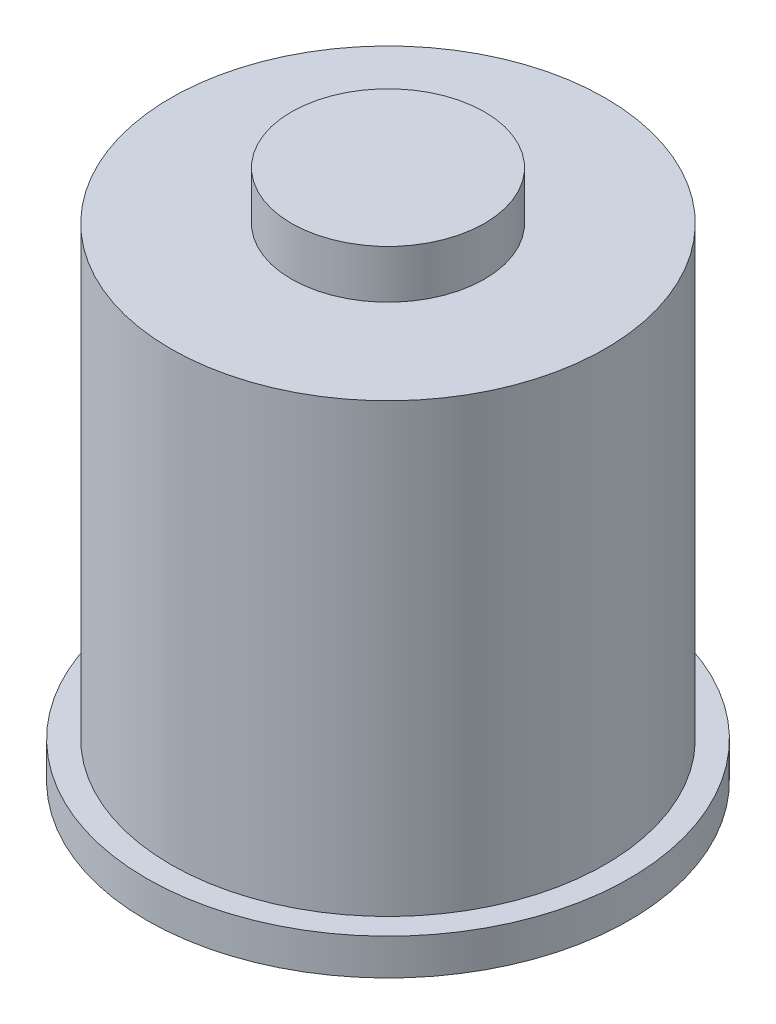
SolidWorks part; units mm, degrees
ref_plane "Plan de face" through (0, 0, 0) normal (0, 0, 1) x (1, 0, 0)
ref_plane "Plan de dessus" through (0, 0, 0) normal (0, 1, 0) x (1, 0, 0)
ref_plane "Plan de droite" through (0, 0, 0) normal (1, 0, 0) x (0, 0, -1)
sketch "Esquisse1" plane through (0, 0, 0) normal (1, 0, 0) x (0, 0, -1)
  line L0 (10, 0) -> (2.5, 0)
  line L1 (0, -2.5) -> (0, 0)
  line L2 (0, 0) -> (0, 20)
  line L3 (0, 20) -> (9, 20) construction
  line L4 (9, 1.5) -> (9, 20) construction
  line L5 (10, 0) -> (10, 1.5)
  line L6 (10, 1.5) -> (9, 1.5)
  line L7 (9, 1.5) -> (9, 20)
  line L8 (0, 20) -> (0, 22)
  line L9 (0, 22) -> (4, 22)
  line L10 (4, 22) -> (4, 20)
  line L11 (4, 20) -> (9, 20)
  arc A0 (2.5, 0) -> (0, -2.5) centre (0, 0) cw
  dimension "D5" = 2.5
  dimension "D1" = 9
  dimension "D2" = 18.5
  dimension "D3" = 2
  dimension "D4" = 1.5
  dimension "D6" = 4
  dimension "D7" = 10
revolve "Révolution1" add sketch "Esquisse1" angle 360 about L2
